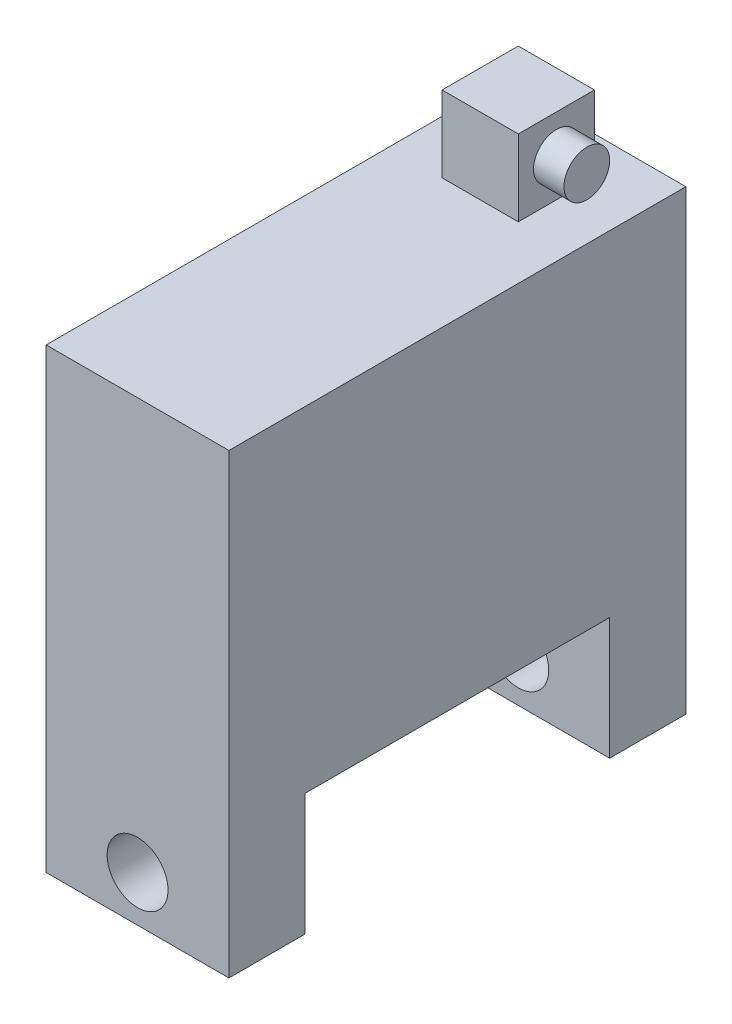
SolidWorks part; units mm, degrees
ref_plane "Front Plane" through (0, 0, 0) normal (0, 0, 1) x (1, 0, 0)
ref_plane "Top Plane" through (0, 0, 0) normal (0, 1, 0) x (1, 0, 0)
ref_plane "Right Plane" through (0, 0, 0) normal (1, 0, 0) x (0, 0, -1)
sketch "Sketch1" plane through (0, 0, 0) normal (0, 1, 0) x (1, 0, 0)
  line L1 (-30, 75) -> (30, 75)
  line L2 (-30, 75) -> (-30, -75)
  line L3 (-30, -75) -> (30, -75)
  line L4 (30, 75) -> (30, -75)
  line L5 (-30, 75) -> (30, -75) construction
  line L6 (-30, -75) -> (30, 75) construction
  point P0 (0, 0)
  dimension "D1" = 60
  dimension "D2" = 150
extrude "Boss-Extrude1" add sketch "Sketch1" along normal blind 150 contours L2 L1 L4 L3
sketch "Sketch2" plane through (0, 0, 0) normal (0, 0, 1) x (1, 0, 0)
  line L0 (0, 0) -> (0, 15) construction
  circle A0 centre (0, 15) radius 10
  dimension "D2" = 20
  dimension "D1" = 15
extrude "Cut-Extrude1" cut sketch "Sketch2" against normal blind 100 and the other way blind 100
sketch "Sketch3" plane through (0, 0, 0) normal (1, 0, 0) x (0, 0, -1)
  line L0 (0, 0) -> (0, 30) construction
  line L3 (-50, -40) -> (50, -40)
  line L4 (-50, -40) -> (-50, 40)
  line L5 (-50, 40) -> (50, 40)
  line L6 (50, -40) -> (50, 40)
  line L7 (-50, -40) -> (50, 40) construction
  line L8 (-50, 40) -> (50, -40) construction
  dimension "D1" = 30
  dimension "D2" = 100
  dimension "D3" = 80
extrude "Cut-Extrude2" cut sketch "Sketch3" against normal blind 100 and the other way blind 100
ref_axis "Axis1" through (0, -39, 0) along (0, 1, 0)
ref_axis "Axis2" through (0, 15, -55) along (0, 0, -1)
sketch "Sketch5" plane through (0, 150, 0) normal (0, 1, 0) x (1, 0, 0)
  line L0 (0, 75) -> (0, 50) construction
  line L1 (-30, 75) -> (30, 75) construction
  line L2 (0, 55) -> (0, 75) construction
  line L4 (-12.5, 62.5) -> (12.5, 62.5)
  line L5 (-12.5, 62.5) -> (-12.5, 37.5)
  line L6 (-12.5, 37.5) -> (12.5, 37.5)
  line L7 (12.5, 62.5) -> (12.5, 37.5)
  line L8 (-12.5, 62.5) -> (12.5, 37.5) construction
  line L9 (-12.5, 37.5) -> (12.5, 62.5) construction
  dimension "D1" = 25
  dimension "D2" = 25
  dimension "D3" = 25
extrude "Boss-Extrude3" add sketch "Sketch5" along normal blind 25
sketch "Sketch6" plane through (12.5, 0, 0) normal (1, 0, 0) x (0, 0, -1)
  circle A0 centre (50, 162.5) radius 7.5
extrude "Boss-Extrude4" add sketch "Sketch6" along normal blind 10
